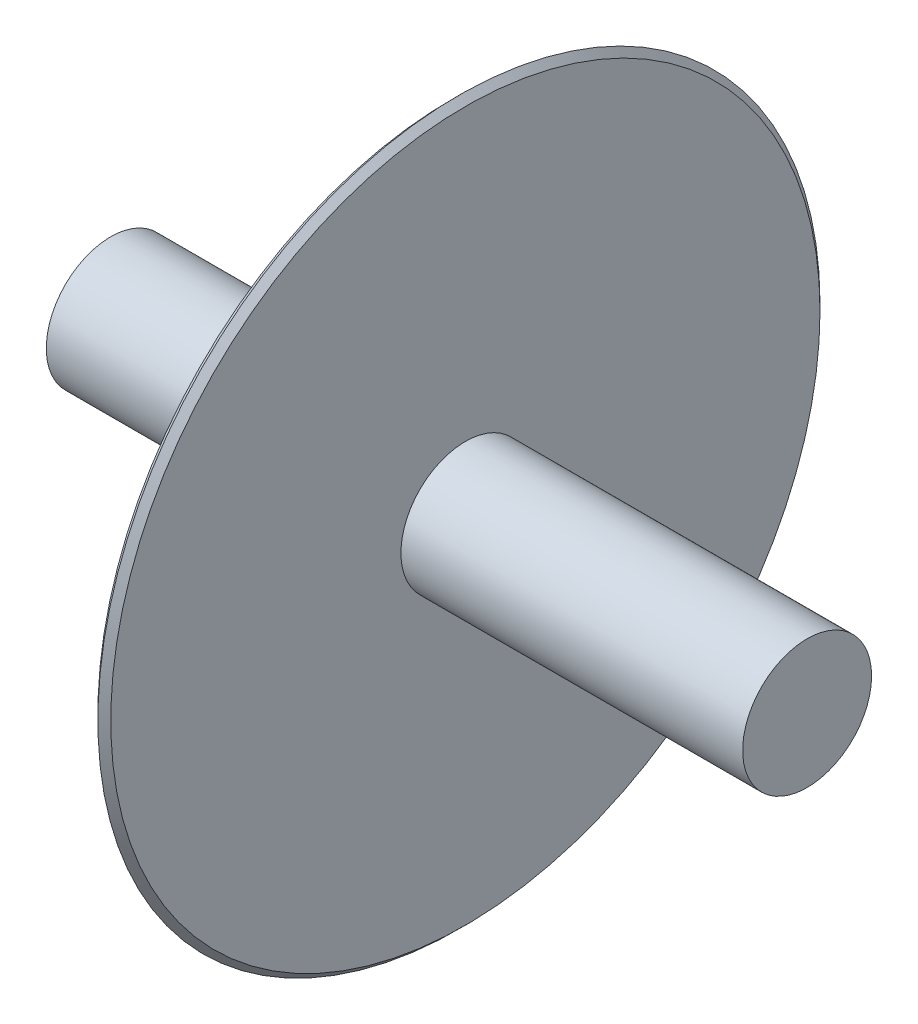
SolidWorks part; units mm, degrees
ref_plane "Front Plane" through (0, 0, 0) normal (0, 0, 1) x (1, 0, 0)
ref_plane "Top Plane" through (0, 0, 0) normal (0, 1, 0) x (1, 0, 0)
ref_plane "Right Plane" through (0, 0, 0) normal (1, 0, 0) x (0, 0, -1)
sketch "Sketch1" plane through (0, 0, 0) normal (1, 0, 0) x (0, 0, -1)
  circle A0 centre (0, 0) radius 2.5
  circle A1 centre (0, 0) radius 14
  dimension "D1" = 5
  dimension "D2" = 28
extrude "Boss-Extrude3" add sketch "Sketch1" along normal mid plane 27 contours A0
sketch "Sketch2" plane through (0, 0, 0) normal (1, 0, 0) x (0, 0, -1)
  circle A0 centre (0, 0) radius 14
  dimension "D1" = 28
extrude "Boss-Extrude4" add sketch "Sketch2" along normal mid plane 0.5
chamfer "Chamfer1" distance 0.25 angle 45 2 edges at (-0.25, 0, -14) (0.25, 0, -14)
